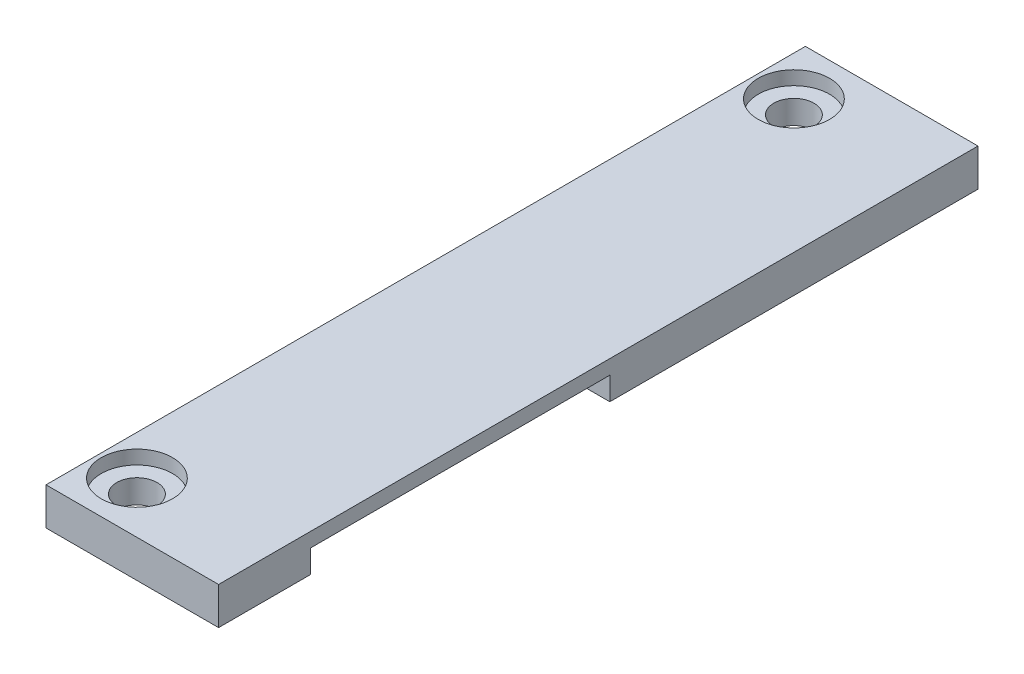
SolidWorks part; units mm, degrees
ref_plane "前视基准面" through (0, 0, 0) normal (0, 0, 1) x (1, 0, 0)
ref_plane "上视基准面" through (0, 0, 0) normal (0, 1, 0) x (1, 0, 0)
ref_plane "右视基准面" through (0, 0, 0) normal (1, 0, 0) x (0, 0, -1)
other "Configuration Table"
sketch "草图1" plane through (0, 0, 0) normal (1, 0, 0) x (0, 0, -1)
  line L5 (-33, 1.625) -> (33, 1.625)
  line L6 (-33, 1.625) -> (-33, -1.625)
  line L7 (-33, -1.625) -> (33, -1.625)
  line L8 (33, 1.625) -> (33, -1.625)
  line L9 (-33, 1.625) -> (33, -1.625) construction
  line L10 (-33, -1.625) -> (33, 1.625) construction
  line L11 (-25, -1.625) -> (1, -1.625)
  line L12 (-25, -1.625) -> (-25, 0.375)
  line L13 (-25, 0.375) -> (1, 0.375)
  line L14 (1, -1.625) -> (1, 0.375)
  point P0 (0, 0)
  dimension "D1" = 3.25
  dimension "D2" = 66
  dimension "D3" = 8
  dimension "D4" = 34
  dimension "D5" = 2
extrude "凸台-拉伸1" add sketch "草图1" along normal blind 15 contours L14 L7 L8 L5 L6 L12 L13 region at (0, 0.2, -3.84)
sketch "草图2" plane through (0, 1.625, 0) normal (0, 1, 0) x (1, 0, 0)
  line L0 (15, -33) -> (0, -33) construction
  circle A0 centre (3.4511, 28.55) radius 1.75
  circle A1 centre (3.4511, -28.55) radius 1.75
  circle A2 centre (3.4511, 28.55) radius 3.1
  circle A3 centre (3.4511, -28.55) radius 3.1
  dimension "D3" = 3.5
  dimension "D4" = 6.2
  dimension "D1" = 57.1
  dimension "D2" = 4.45
extrude "切除-拉伸1" cut sketch "草图2" against normal through all contours A1 | A0 region at (3.4511, 1.625, -28.55) region at (3.4511, 1.625, 28.55)
extrude "切除-拉伸2" cut sketch "草图2<3>" against normal blind 1.2
sketch "草图2<3>" plane through (0, 1.625, 0) normal (0, 1, 0) x (1, 0, 0) same geometry as "草图2"
